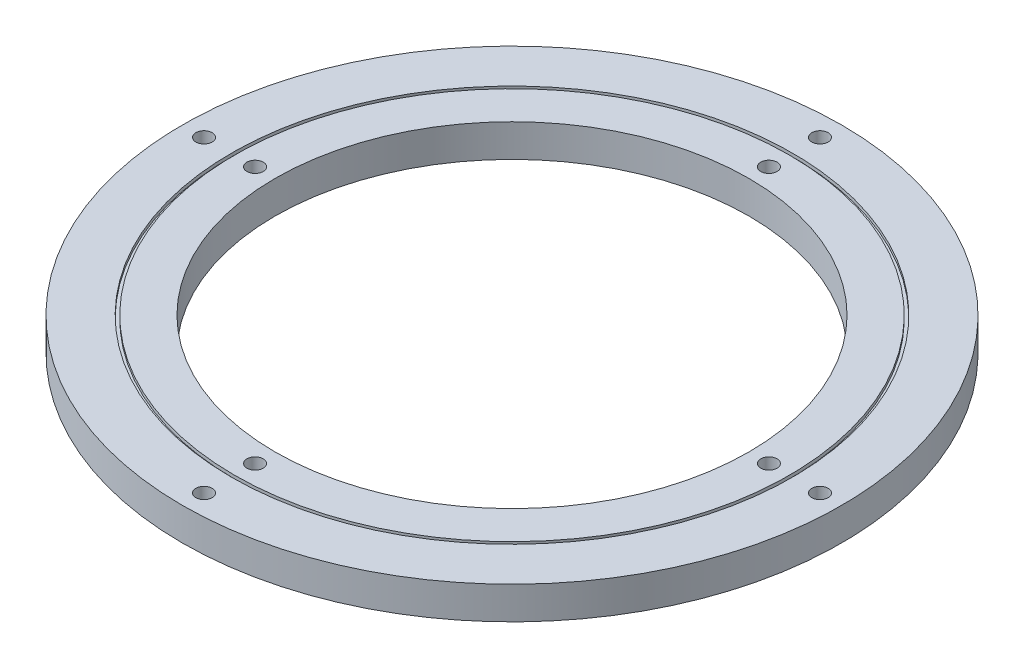
SolidWorks part; units mm, degrees
ref_plane "Front Plane" through (0, 0, 0) normal (0, 0, 1) x (1, 0, 0)
ref_plane "Top Plane" through (0, 0, 0) normal (0, 1, 0) x (1, 0, 0)
ref_plane "Right Plane" through (0, 0, 0) normal (1, 0, 0) x (0, 0, -1)
sketch "Sketch1" plane through (0, 0, 0) normal (0, 1, 0) x (1, 0, 0)
  circle A0 centre (0, 0) radius 101.0285
  circle A1 centre (0, 0) radius 72.6313
  dimension "D1" = 202.057
  dimension "D2" = 28.3972
extrude "Boss-Extrude1" add sketch "Sketch1" along normal blind 10
sketch "Sketch2" plane through (0, 10, 0) normal (0, 1, 0) x (1, 0, 0)
  line L0 (0, 0) -> (-78.7635, 0) construction
  line L1 (0, 0) -> (0, 78.7635) construction
  circle A0 centre (0, 0) radius 78.7635 construction
  circle A1 centre (0, 0) radius 72.6313 construction
  circle A2 centre (0, 0) radius 94.4137 construction
  circle A3 centre (0, 0) radius 101.0285 construction
  circle A4 centre (-94.4137, 0) radius 2.5
  circle A5 centre (-78.7635, 0) radius 2.5
  circle A6 centre (0, 78.7635) radius 2.5
  circle A7 centre (0, 94.4137) radius 2.5
  circle A8 centre (78.7635, 0) radius 2.5
  circle A9 centre (94.4137, 0) radius 2.5
  circle A10 centre (0, -78.7635) radius 2.5
  circle A11 centre (0, -94.4137) radius 2.5
  dimension "D1" = 6.1322
  dimension "D2" = 6.6148
  dimension "D3" = 5
  dimension "D5" = 90
  dimension "D4" = 4
extrude "Cut-Extrude1" cut sketch "Sketch2" against normal through all
sketch "Sketch3" plane through (0, 10, 0) normal (0, 1, 0) x (1, 0, 0)
  circle A0 centre (0, 0) radius 86.0285
  circle A1 centre (0, 0) radius 85.0285
  circle A2 centre (0, 0) radius 101.0285 construction
  dimension "D1" = 1
  dimension "D2" = 15
extrude "Cut-Extrude2" cut sketch "Sketch3" against normal blind 1
ref_plane "Plane1" through (0, 5, 0) normal (0, 1, 0) x (1, 0, 0)
mirror "Mirror1" about plane through (0, 5, 0) normal (0, 1, 0) of "Cut-Extrude2"
ref_axis "Axis1" through (0, 10, 0) along (0, -1, 0)
